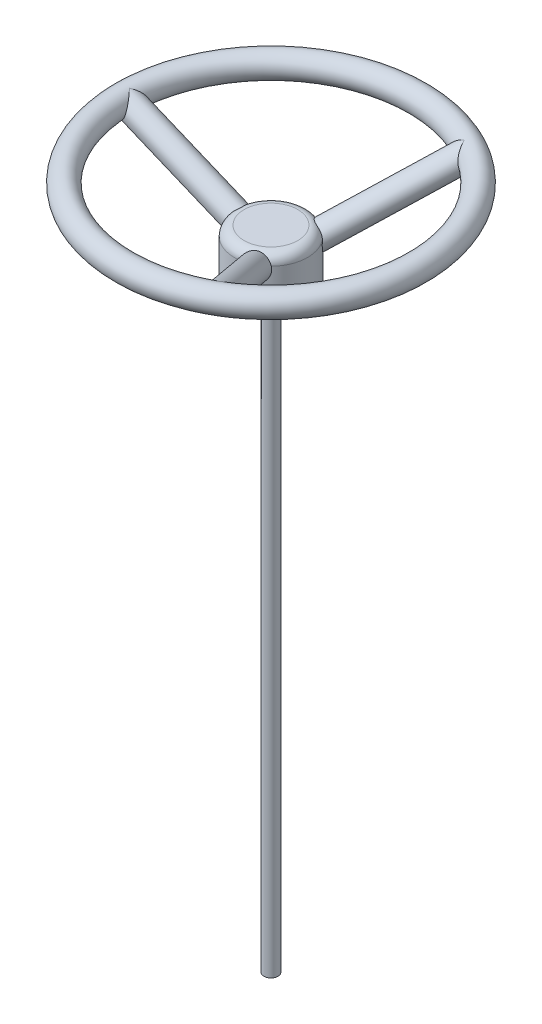
SolidWorks part; units mm, degrees
ref_plane "Front Plane" through (0, 0, 0) normal (0, 0, 1) x (1, 0, 0)
ref_plane "Top Plane" through (0, 0, 0) normal (0, 1, 0) x (1, 0, 0)
ref_plane "Right Plane" through (0, 0, 0) normal (1, 0, 0) x (0, 0, -1)
sketch "Sketch1" plane through (0, 0, 0) normal (0, 0, 1) x (1, 0, 0)
  line L0 (0, 0) -> (152.4, 0) construction
  line L1 (152.4, -24.1715) -> (152.4, 24.1715) construction
  circle A0 centre (0, 0) radius 12.7
  point P7 (152.4, 0)
  dimension "D1" = 25.4
  dimension "D2" = 152.4
revolve "Revolve1" add sketch "Sketch1" angle 360 about L1
sketch "Sketch3" plane through (0, 0, 0) normal (0, 1, 0) x (1, 0, 0)
  circle A0 centre (152.4, 0) radius 38.1 construction
  dimension "D1" = 76.2
  dimension "D2" = 152.4
ref_plane "Plane1" through (0, -38.1, 0) normal (0, 1, 0) x (1, 0, 0)
sketch "Sketch4" plane through (0, -38.1, 0) normal (0, 1, 0) x (1, 0, 0)
  circle A0 centre (152.4, 0) radius 38.1
extrude "Boss-Extrude1" add sketch "Sketch4" against normal blind 50.8 separate body
sketch3d "3DSketch1"
  line L0 (114.369, -50.8, -2.2918) -> (0, 0, 0)
  line L1 (114.369, -38.1, -2.2918) -> (114.369, -50.8, -2.2918) construction
  circle A0 centre (152.4, -38.1, 0) radius 38.1 construction
  point P5 (152.4, 0, 0)
  dimension "D1" = 12.7
sweep "Sweep1" add path "3DSketch1" circular profile diameter 25.4 parameters "D3"=25.4
sketch "Sketch13" plane through (114.369, -50.8, -2.2918) normal (0.9137, -0.4059, -0.0183) x (-0.0167, 0.0074, -0.9998)
  circle A0 centre (0, 0) radius 12.7
extrude "Boss-Extrude2" add sketch "Sketch13" along normal blind 50.8
pattern_circular "CirPattern1" count 3 over 360 about axis through (152.4, -38.1, 0) along (0, 1, 0) of "Sweep1", "Boss-Extrude2"
sketch "Sketch20" plane through (0, -88.9, 0) normal (0, -1, 0) x (-1, 0, 0)
  circle A0 centre (-152.4, 0) radius 7.3025
  dimension "D1" = 14.605
extrude "Boss-Extrude3" add sketch "Sketch20" along normal blind 622.3
fillet "Fillet1" radius 10.16 2 edges at (131.6681, -38.1, 31.9656) (190.449, -38.1, 1.9716)
